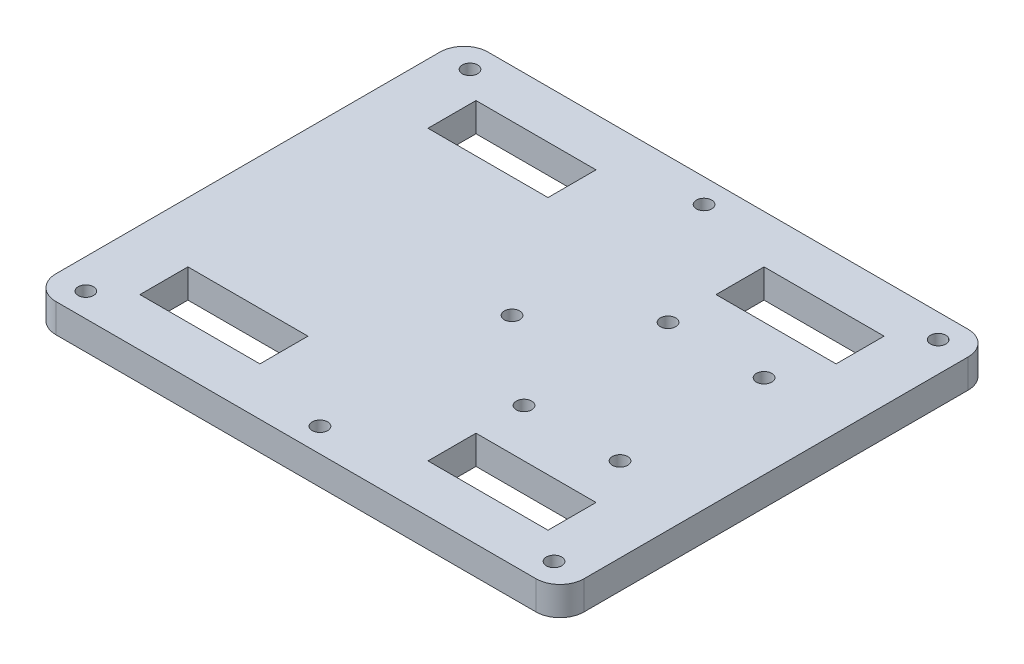
SolidWorks part; units mm, degrees
material "Maple"
ref_plane "Front Plane" through (0, 0, 0) normal (0, 0, 1) x (1, 0, 0)
ref_plane "Top Plane" through (0, 0, 0) normal (0, 1, 0) x (1, 0, 0)
ref_plane "Right Plane" through (0, 0, 0) normal (1, 0, 0) x (0, 0, -1)
sketch "Sketch1" plane through (0, 0, 0) normal (0, 1, 0) x (1, 0, 0)
  line L0 (-55, 0) -> (55, 0) construction
  line L1 (-55, 45) -> (55, 45)
  line L2 (-55, 45) -> (-55, -45)
  line L3 (-55, -45) -> (55, -45)
  line L4 (55, 45) -> (55, -45)
  point P0 (0, 0)
  dimension "D1" = 90
  dimension "D2" = 110
extrude "Boss-Extrude1" add sketch "Sketch1" along normal blind 6
sketch "Sketch2" plane through (0, 6, 0) normal (0, 1, 0) x (1, 0, 0)
  line L0 (-55, 0) -> (55, 0) construction
  line L1 (-55, 45) -> (-55, -45) construction
  line L2 (55, -45) -> (55, 45) construction
  line L3 (0, 0) -> (0, 45) construction
  line L4 (17.5, 35) -> (42.5, 35)
  line L5 (17.5, 35) -> (17.5, 25)
  line L6 (17.5, 25) -> (42.5, 25)
  line L7 (42.5, 35) -> (42.5, 25)
  line L8 (17.5, 35) -> (42.5, 25) construction
  line L9 (17.5, 25) -> (42.5, 35) construction
  line L10 (55, 45) -> (-55, 45) construction
  point P6 (30, 30)
  dimension "D1" = 10
  dimension "D2" = 60
  dimension "D3" = 60
  dimension "D4" = 25
extrude "Cut-Extrude1" cut sketch "Sketch2" against normal through all
mirror "Mirror1" about plane through (0, 0, 0) normal (0, 0, 1) of "Cut-Extrude1"
mirror "Mirror2" about plane through (0, 0, 0) normal (1, 0, 0) of "Mirror1", "Cut-Extrude1"
hole_wizard "M3 Clearance Hole1" positions "Sketch4" profile "Sketch3" hole size "M3" standard "ANSI Metric" end condition through all
sketch "Sketch4" plane through (0, 6, 0) normal (0, 1, 0) x (1, 0, 0)
  line L0 (13.7067, -15) -> (41.2933, -15) construction
  line L1 (13.7067, 15) -> (41.2933, 15) construction
  line L3 (17.5, 15) -> (17.5, -15) construction
  line L5 (37.5, 15) -> (37.5, -15) construction
  line L7 (27.5, 15) -> (27.5, -15) construction
  point P0 (17.5, 15)
  point P2 (37.5, 15)
  point P4 (17.5, -15)
  point P6 (37.5, -15)
  dimension "D2" = 20
sketch "Sketch3" plane through (17.5, 6, -15) normal (1, 0, 0) x (0, 0, 1)
  line L0 (0, 0) -> (0, 6)
  line L1 (0, 6) -> (1.6, 6)
  line L2 (1.6, 6) -> (1.6, 0)
  line L5 (1.6, 0) -> (0, 0)
  line L11 (0, -6.35) -> (0, 107.95) construction
  dimension "Thru Hole Dia." = 3.2
  dimension "Thru Hole Depth" = 6
hole_wizard "M3 Clearance Hole2" positions "Sketch6" profile "Sketch5" hole size "M3" standard "ANSI Metric" end condition through all
sketch "Sketch6" plane through (0, 6, 0) normal (0, 1, 0) x (1, 0, 0)
  line L0 (-48.75, -40) -> (-48.75, 40) construction
  line L1 (-48.75, 40) -> (48.75, 40) construction
  line L2 (48.75, 40) -> (48.75, -40) construction
  line L3 (48.75, -40) -> (-48.75, -40) construction
  line L5 (-48.75, 40) -> (48.75, -40) construction
  line L7 (-48.75, -40) -> (48.75, 40) construction
  line L9 (-30, 35) -> (-30, 40) construction
  line L10 (-42.5, 35) -> (-17.5, 35) construction
  line L11 (-30, 40) -> (-30, 45) construction
  line L12 (55, 45) -> (-55, 45) construction
  line L14 (-42.5, 30) -> (-48.75, 30) construction
  line L15 (-42.5, 25) -> (-42.5, 35) construction
  line L16 (-48.75, 30) -> (-55, 30) construction
  line L17 (-55, 45) -> (-55, -45) construction
  point P0 (48.75, 40)
  point P2 (0, 40)
  point P4 (-48.75, 40)
  point P6 (-48.75, -40)
  point P8 (0, -40)
  point P10 (48.75, -40)
  point P12 (0, 0)
sketch "Sketch5" plane through (48.75, 6, -40) normal (1, 0, 0) x (0, 0, 1)
  line L0 (0, 0) -> (0, 6)
  line L1 (0, 6) -> (1.6, 6)
  line L2 (1.6, 6) -> (1.6, 0)
  line L5 (1.6, 0) -> (0, 0)
  line L11 (0, -6.35) -> (0, 107.95) construction
  dimension "Thru Hole Dia." = 3.2
  dimension "Thru Hole Depth" = 6
fillet "Fillet1" radius 5 4 edges at (55, 3, 45) (-55, 3, 45) (55, 3, -45) (-55, 3, -45)
sketch "Sketch7" plane through (0, 6, 0) normal (0, 1, 0) x (1, 0, 0)
  line L0 (-157.4189, 4.54) -> (-45, 4.54) construction
  line L1 (-157.4189, 6.04) -> (-157.4189, 3.04) construction
  line L2 (-55, 5.29) -> (-45, 5.29)
  line L3 (-55, 40) -> (-55, -40) construction
  line L4 (-45, 5.29) -> (-45, 3.79)
  line L5 (-45, 3.79) -> (-55, 3.79)
  line L6 (-55, 3.79) -> (-55, 5.29)
  dimension "D1" = 1.5
  dimension "D2" = 10
extrude "Cut-Extrude2" [suppressed] cut sketch "Sketch7" against normal through all
